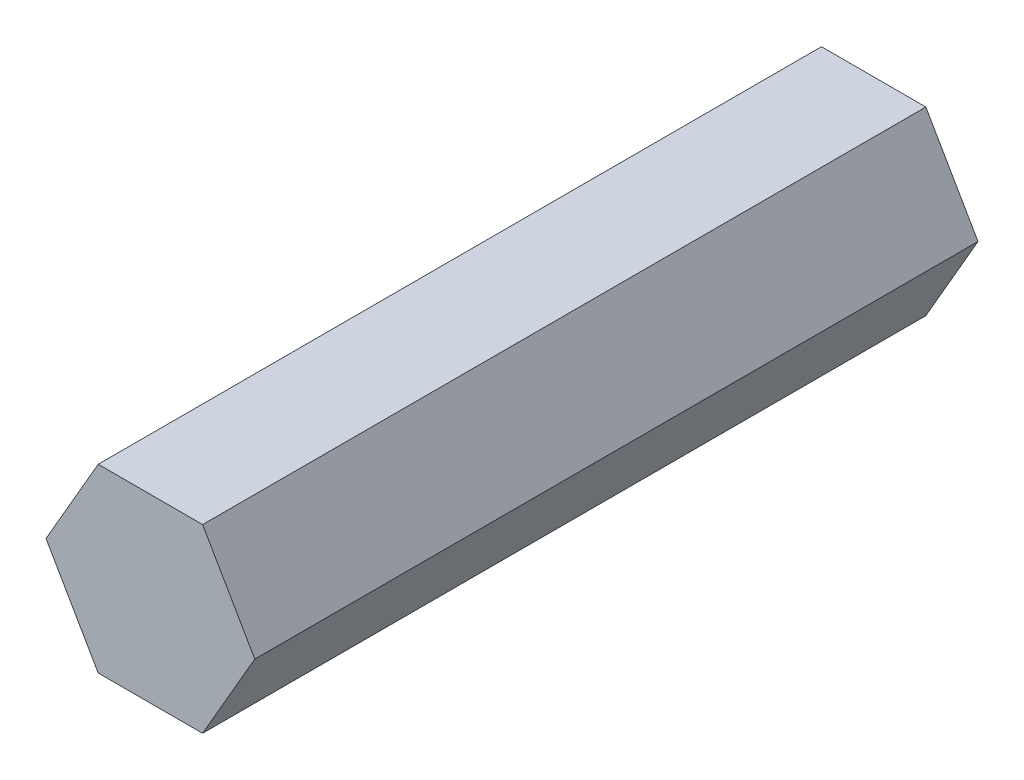
SolidWorks part; units mm, degrees
ref_plane "Front Plane" through (0, 0, 0) normal (0, 0, 1) x (1, 0, 0)
ref_plane "Top Plane" through (0, 0, 0) normal (0, 1, 0) x (1, 0, 0)
ref_plane "Right Plane" through (0, 0, 0) normal (1, 0, 0) x (0, 0, -1)
sketch "Sketch1" plane through (0, 0, 0) normal (0, 0, 1) x (1, 0, 0)
  line L1 (3.6635, -6.3515) -> (7.3323, -0.003)
  line L2 (7.3323, -0.003) -> (3.6688, 6.3485)
  line L3 (3.6688, 6.3485) -> (-3.6635, 6.3515)
  line L4 (-3.6635, 6.3515) -> (-7.3323, 0.003)
  line L5 (-7.3323, 0.003) -> (-3.6688, -6.3485)
  line L6 (-3.6688, -6.3485) -> (3.6635, -6.3515)
  circle A0 centre (0, 0) radius 6.35 construction
  dimension "D1" = 12.7
extrude "Boss-Extrude1" add sketch "Sketch1" along normal blind 50.8
sketch "Sketch2" plane through (0, 0, 0) normal (0, 0, -1) x (-1, 0, 0)
  circle A0 centre (0, 0) radius 6.35
